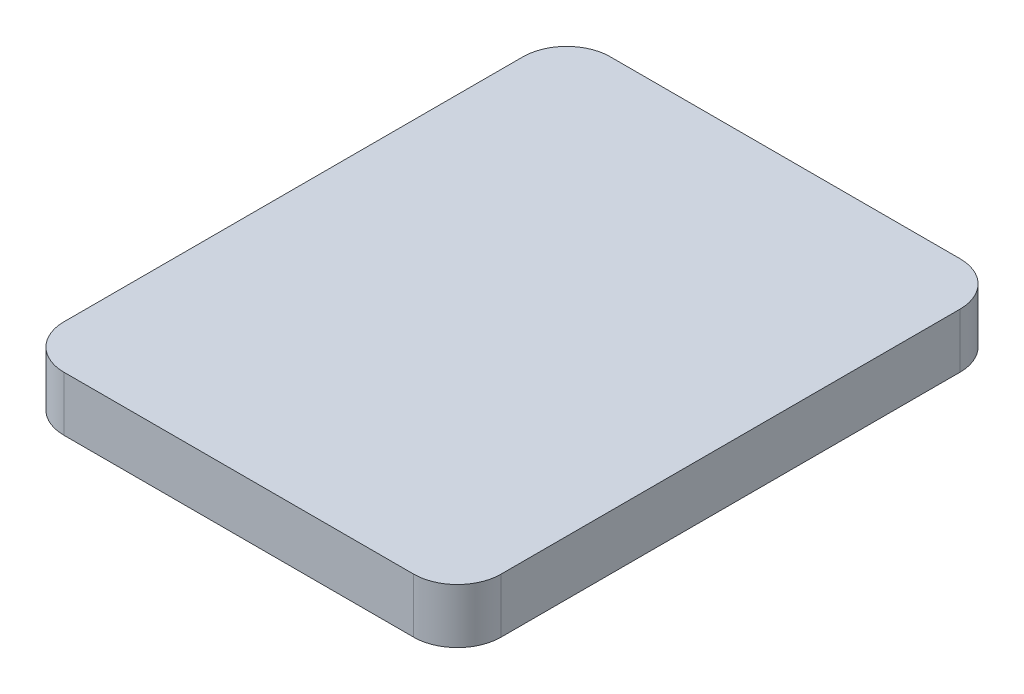
SolidWorks part; units mm, degrees
material "Acrylic (Medium-high impact)"
ref_plane "Front Plane" through (0, 0, 0) normal (0, 0, 1) x (1, 0, 0)
ref_plane "Top Plane" through (0, 0, 0) normal (0, 1, 0) x (1, 0, 0)
ref_plane "Right Plane" through (0, 0, 0) normal (1, 0, 0) x (0, 0, -1)
ref_plane "Plane1" through (0, 0, 0) normal (0, 1, 0) x (1, 0, 0)
sketch "Sketch1" plane through (0, 0, 0) normal (0, 1, 0) x (1, 0, 0)
  line L1 (0, 0) -> (25.4, 0)
  line L2 (0, 0) -> (0, 31.75)
  line L3 (0, 31.75) -> (25.4, 31.75)
  line L4 (25.4, 0) -> (25.4, 31.75)
  dimension "D1" = 31.75
  dimension "D2" = 25.4
extrude "Boss-Extrude1" add sketch "Sketch1" along normal blind 3.175
ref_plane "Plane2" through (0, 3.175, 0) normal (0, 1, 0) x (1, 0, 0)
sketch "Sketch2" plane through (0, 3.175, 0) normal (0, 1, 0) x (1, 0, 0)
  line L1 (6.35, 25.4) -> (19.05, 25.4)
  line L2 (6.35, 25.4) -> (6.35, 22.225)
  line L3 (6.35, 22.225) -> (19.05, 22.225)
  line L4 (19.05, 25.4) -> (19.05, 22.225)
  line L5 (0, 31.75) -> (0, 0) construction
  line L6 (25.4, 31.75) -> (0, 31.75) construction
  dimension "D1" = 12.7
  dimension "D2" = 3.175
  dimension "D3" = 6.35
  dimension "D4" = 6.35
extrude "Cut-Extrude1" [suppressed] cut sketch "Sketch2" against normal through all
fillet "Fillet1" radius 2.54 4 edges at (0, 1.5875, -31.75) (25.4, 1.5875, -31.75) (25.4, 1.5875, 0) (0, 1.5875, 0)
